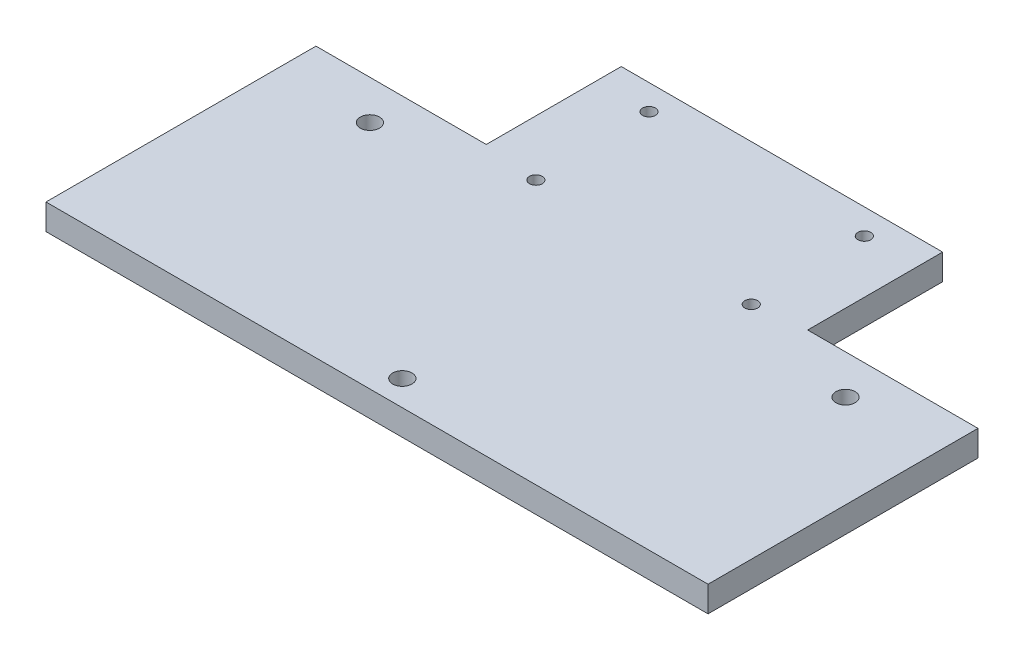
SolidWorks part; units mm, degrees
ref_plane "Front Plane" through (0, 0, 0) normal (0, 0, 1) x (1, 0, 0)
ref_plane "Top Plane" through (0, 0, 0) normal (0, 1, 0) x (1, 0, 0)
ref_plane "Right Plane" through (0, 0, 0) normal (1, 0, 0) x (0, 0, -1)
sketch "Sketch1" plane through (0, 0, 0) normal (0, 1, 0) x (1, 0, 0)
  line L0 (-47.6178, 3.1383) -> (55.3822, 3.1383) construction
  line L1 (-47.6178, 13.1383) -> (-21.1178, 13.1383)
  line L2 (-47.6178, 13.1383) -> (-47.6178, -28.8617)
  line L3 (-47.6178, -28.8617) -> (55.3822, -28.8617)
  line L4 (55.3822, 13.1383) -> (55.3822, -28.8617)
  line L5 (-47.6178, -18.8617) -> (55.3822, -18.8617) construction
  line L6 (-47.6178, -7.8617) -> (55.3822, -7.8617) construction
  line L7 (3.8822, 11.1383) -> (3.8822, -28.8617) construction
  line L8 (-21.1178, 13.1383) -> (-21.1178, 34.1383)
  line L9 (-21.1178, 34.1383) -> (28.8822, 34.1383)
  line L10 (28.8822, 34.1383) -> (28.8822, 13.1383)
  line L11 (28.8822, 13.1383) -> (55.3822, 13.1383)
  line L12 (3.8822, 34.1383) -> (3.8822, 11.1383) construction
  circle A0 centre (-33.1178, 7.0284) radius 1.5
  circle A1 centre (40.8822, 7.0284) radius 1.5
  circle A2 centre (3.8822, -24.9268) radius 1.5
  circle A3 centre (-12.8678, 30.2027) radius 1
  circle A4 centre (20.6322, 30.2027) radius 1
  circle A5 centre (-12.4651, 12.2072) radius 1
  circle A6 centre (21.0349, 12.2072) radius 1
  point P31 (21.6322, 30.2027)
  point P32 (0, 0)
  point P33 (0, 0)
  dimension "D5" = 37
  dimension "D6" = 3
  dimension "D7" = 50
  dimension "D8" = 2
  dimension "D11" = 21
  dimension "D1" = 103
  dimension "D2" = 42
  dimension "D3" = 22
  dimension "D4" = 11
  dimension "D9" = 33.5
  dimension "D10" = 18
  dimension "D12" = 33.5
extrude "Boss-Extrude1" add sketch "Sketch1" along normal blind 4
